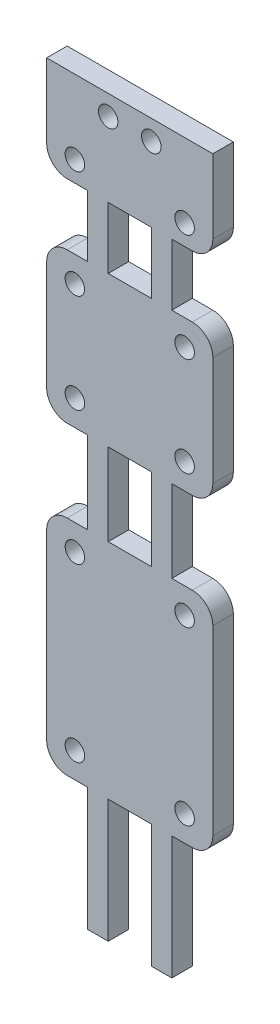
SolidWorks part; units mm, degrees
ref_plane "Front Plane" through (0, 0, 0) normal (0, 0, 1) x (1, 0, 0)
ref_plane "Top Plane" through (0, 0, 0) normal (0, 1, 0) x (1, 0, 0)
ref_plane "Right Plane" through (0, 0, 0) normal (1, 0, 0) x (0, 0, -1)
sketch "Sketch1" plane through (0, 0, 0) normal (0, 0, 1) x (1, 0, 0)
  line L0 (0, 1.5) -> (0, 14) construction
  line L1 (16.2, 1.5) -> (16.2, 14) construction
  line L2 (2, 47.74) -> (4, 47.74)
  line L3 (0, 1.5) -> (16.2, 1.5) construction
  line L4 (0, 14) -> (4, 14) construction
  line L5 (2, 26) -> (4, 26)
  line L6 (16.2, 85.59) -> (0, 85.59)
  line L7 (2, 70.385) -> (4, 70.385)
  line L8 (2, 55.74) -> (4, 55.74)
  line L9 (0, 28) -> (0, 45.74)
  line L10 (2, 76.385) -> (4, 76.385)
  line L11 (16.2, 28) -> (16.2, 45.74)
  line L12 (16.2, 57.74) -> (16.2, 68.385)
  line L13 (0, 57.74) -> (0, 68.385)
  line L14 (16.2, 78.385) -> (16.2, 85.59)
  line L15 (0, 78.385) -> (0, 85.59)
  line L16 (6, 70.385) -> (6, 76.385)
  line L17 (4, 55.74) -> (4, 47.74)
  line L18 (4, 70.385) -> (4, 76.385)
  line L19 (6, 55.74) -> (6, 47.74)
  line L20 (4, 26) -> (4, 14)
  line L21 (6, 26) -> (6, 14)
  line L22 (8.1, 1.5) -> (8.1, 85.59) construction
  line L23 (10.2, 26) -> (10.2, 14)
  line L24 (12.2, 26) -> (12.2, 14)
  line L25 (10.2, 55.74) -> (10.2, 47.74)
  line L26 (12.2, 55.74) -> (12.2, 47.74)
  line L27 (10.2, 70.385) -> (10.2, 76.385)
  line L28 (12.2, 70.385) -> (12.2, 76.385)
  line L29 (6, 26) -> (10.2, 26)
  line L30 (6, 14) -> (10.2, 14) construction
  line L31 (12.2, 14) -> (16.2, 14) construction
  line L32 (12.2, 26) -> (14.2, 26)
  line L33 (12.2, 47.74) -> (14.2, 47.74)
  line L34 (6, 47.74) -> (10.2, 47.74)
  line L35 (12.2, 76.385) -> (14.2, 76.385)
  line L36 (6, 76.385) -> (10.2, 76.385)
  line L37 (6, 70.385) -> (10.2, 70.385)
  line L38 (12.2, 70.385) -> (14.2, 70.385)
  line L39 (12.2, 55.74) -> (14.2, 55.74)
  line L40 (6, 55.74) -> (10.2, 55.74)
  line L41 (4, 14) -> (6, 14)
  line L42 (10.2, 14) -> (12.2, 14)
  circle A0 centre (13.45, 45.24) radius 0.95
  circle A1 centre (2.75, 67.885) radius 0.95
  circle A2 centre (13.45, 58.24) radius 0.95
  circle A3 centre (13.45, 78.385) radius 0.95
  circle A4 centre (2.75, 28.5) radius 0.95
  circle A5 centre (2.75, 78.385) radius 0.95
  circle A6 centre (2.75, 58.24) radius 0.95
  circle A7 centre (2.85, 11.5) radius 0.95 construction
  circle A8 centre (13.35, 11.5) radius 0.95 construction
  circle A9 centre (13.35, 5.5) radius 0.95 construction
  circle A10 centre (2.85, 5.5) radius 0.95 construction
  circle A11 centre (6, 83.635) radius 0.95
  circle A12 centre (13.45, 28.5) radius 0.95
  circle A13 centre (13.45, 67.885) radius 0.95
  circle A14 centre (10.2, 83.635) radius 0.95
  circle A15 centre (2.75, 45.24) radius 0.95
  arc A16 (0, 28) -> (2, 26) centre (2, 28) ccw
  arc A17 (16.2, 28) -> (14.2, 26) centre (14.2, 28) cw
  arc A18 (16.2, 45.74) -> (14.2, 47.74) centre (14.2, 45.74) ccw
  arc A19 (0, 45.74) -> (2, 47.74) centre (2, 45.74) cw
  arc A20 (0, 57.74) -> (2, 55.74) centre (2, 57.74) ccw
  arc A21 (16.2, 57.74) -> (14.2, 55.74) centre (14.2, 57.74) cw
  arc A22 (0, 68.385) -> (2, 70.385) centre (2, 68.385) cw
  arc A23 (16.2, 68.385) -> (14.2, 70.385) centre (14.2, 68.385) ccw
  arc A24 (16.2, 78.385) -> (14.2, 76.385) centre (14.2, 78.385) cw
  arc A25 (2, 76.385) -> (0, 78.385) centre (2, 78.385) cw
  point P77 (0, 26)
  point P80 (16.2, 26)
  point P83 (16.2, 47.74)
  point P86 (0, 47.74)
  point P89 (0, 55.74)
  point P92 (16.2, 55.74)
  point P95 (0, 70.385)
  point P98 (16.2, 70.385)
  point P101 (16.2, 76.385)
  point P104 (0, 76.385)
  dimension "D40" = 2
  dimension "D41" = 1.9
  dimension "D1" = 4
  dimension "D2" = 4
  dimension "D3" = 6
  dimension "D4" = 6
  dimension "D5" = 2.5
  dimension "D6" = 12
  dimension "D7" = 2.85
  dimension "D8" = 2.85
  dimension "D9" = 2.85
  dimension "D10" = 16.2
  dimension "D11" = 21.74
  dimension "D12" = 2.75
  dimension "D13" = 2.75
  dimension "D14" = 2.75
  dimension "D15" = 2.75
  dimension "D16" = 2.5
  dimension "D17" = 2.5
  dimension "D18" = 2.5
  dimension "D19" = 2.5
  dimension "D20" = 8
  dimension "D21" = 14.645
  dimension "D22" = 2.75
  dimension "D23" = 2.75
  dimension "D24" = 2.5
  dimension "D25" = 2.5
  dimension "D26" = 2.5
  dimension "D27" = 2.5
  dimension "D28" = 2.75
  dimension "D29" = 2.75
  dimension "D30" = 6
  dimension "D31" = 9.205
  dimension "D32" = 2.75
  dimension "D33" = 6
  dimension "D34" = 2
  dimension "D35" = 7.25
  dimension "D36" = 2
  dimension "D37" = 7.25
  dimension "D38" = 6
  dimension "D39" = 2.75
extrude "Boss-Extrude1" add sketch "Sketch1" along normal blind 2
sketch "Sketch2" plane through (0, 0, 2) normal (0, 0, 1) x (1, 0, 0)
  line L0 (4, 76.385) -> (12.2, 76.385)
  line L1 (12.2, 76.385) -> (12.2, 70.385)
  line L2 (12.2, 70.385) -> (4, 70.385)
  line L3 (4, 70.385) -> (4, 76.385)
  line L4 (4, 55.74) -> (12.2, 55.74)
  line L5 (12.2, 55.74) -> (12.2, 47.74)
  line L6 (12.2, 47.74) -> (4, 47.74)
  line L7 (4, 47.74) -> (4, 55.74)
  line L8 (4, 26) -> (12.2, 26)
  line L9 (12.2, 26) -> (12.2, 14)
  line L10 (12.2, 14) -> (4, 14)
  line L11 (4, 14) -> (4, 26)
extrude "Cut-Extrude1" [suppressed] cut sketch "Sketch2" against normal up to surface (2 mm away) up to face at (8.1, 73.385, 0)
equation "\"D11@Sketch1\"= \"HL@parametersSketch@prostheticParameters.SLDPRT\" * 0.204 - 4 - 12 'Pinky PIP Length"
equation "\"D21@Sketch1\"= \"HL@parametersSketch@prostheticParameters.SLDPRT\" * 0.117 - 4 - 3 'Pinky MIP Length"
equation "\"D31@Sketch1\"= \"HL@parametersSketch@prostheticParameters.SLDPRT\" * 0.093 - 3 - 5'Pinky DIP Length"
equation "\"D10@Sketch1\"= \"fingerWidth@parametersSketch@prostheticParameters.SLDPRT\"'Pinky Width"
equation "\"D41@Sketch1\"= 1.5 + \"tol1@parametersSketch@prostheticParameters.SLDPRT\""
